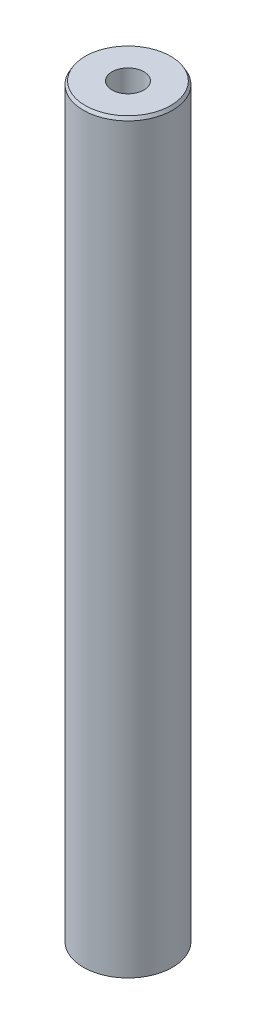
SolidWorks part; units mm, degrees
ref_plane "Front Plane" through (0, 0, 0) normal (0, 0, 1) x (1, 0, 0)
ref_plane "Top Plane" through (0, 0, 0) normal (0, 1, 0) x (1, 0, 0)
ref_plane "Right Plane" through (0, 0, 0) normal (1, 0, 0) x (0, 0, -1)
sketch "Sketch1" plane through (0, 0, 0) normal (0, 1, 0) x (1, 0, 0)
  circle A0 centre (0, 0) radius 25
  dimension "SHAFT_OD" = 50
extrude "Boss-Extrude1" add sketch "Sketch1" along normal blind 419.2389
sketch "Sketch2" plane through (0, 0, 0) normal (0, 1, 0) x (1, 0, 0)
  circle A0 centre (0, 0) radius 8.9193
  dimension "BORE_D" = 17.8387
extrude "Cut-Extrude1" cut sketch "Sketch2" along normal through all
chamfer "Chamfer1" distance 1.7872 angle 30 2 edges at (0, 419.2389, 25) (0, 0, 25) first distance on face at (0, 419.2389, 25) first distance on face at (0, 0, 8.9193)
